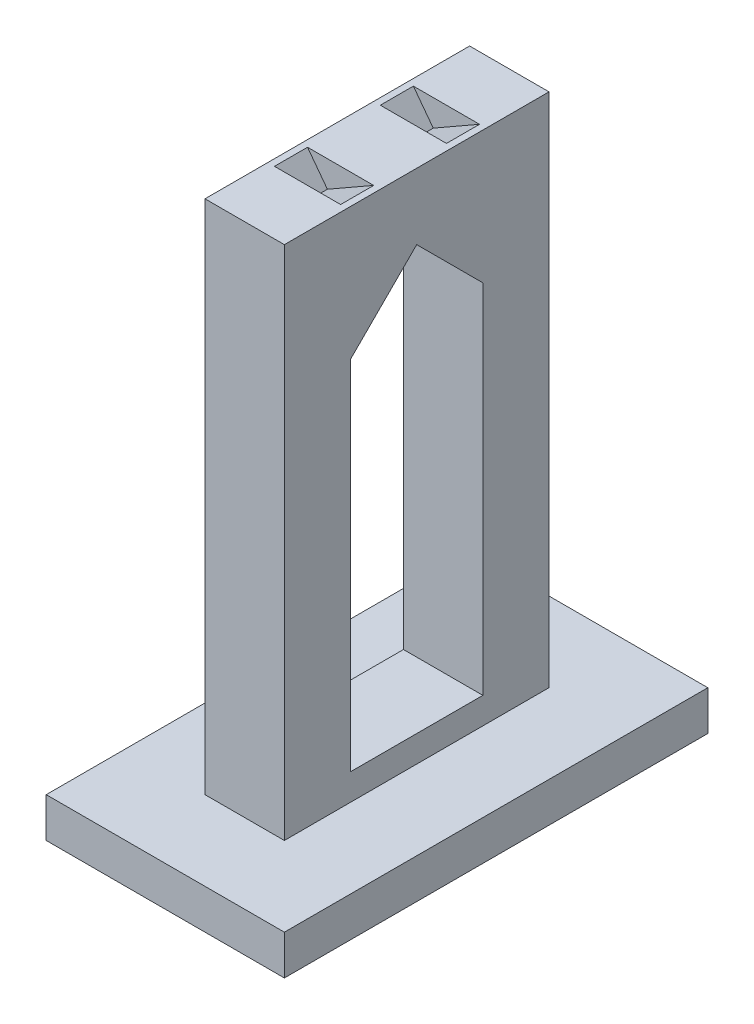
SolidWorks part; units mm, degrees
material "ABS"
ref_plane "Front Plane" through (0, 0, 0) normal (0, 0, 1) x (1, 0, 0)
ref_plane "Top Plane" through (0, 0, 0) normal (0, 1, 0) x (1, 0, 0)
ref_plane "Right Plane" through (0, 0, 0) normal (1, 0, 0) x (0, 0, -1)
sketch "Sketch2" plane through (0, 0, 0) normal (1, 0, 0) x (0, 0, -1)
  line L1 (-12.7, 53.34) -> (12.7, 53.34)
  line L2 (-12.7, 53.34) -> (-12.7, 0)
  line L3 (-12.7, 0) -> (12.7, 0)
  line L4 (12.7, 53.34) -> (12.7, 0)
  point P4 (0, 0)
  dimension "D1" = 25.4
  dimension "D2" = 2.54
extrude "Boss-Extrude1" add sketch "Sketch2" along normal mid plane 7.62
sketch "Sketch5" plane through (3.81, 0, 0) normal (1, 0, 0) x (0, 0, -1)
  line L8 (-6.35, 6.35) -> (6.35, 6.35)
  line L9 (6.35, 6.35) -> (6.35, 46.99)
  line L10 (6.35, 46.99) -> (-6.35, 46.99)
  line L11 (-6.35, 46.99) -> (-6.35, 6.35)
  line L13 (6.35, 6.35) -> (6.35, 46.99)
  line L14 (6.35, 46.99) -> (-6.35, 46.99)
  line L15 (-6.35, 46.99) -> (-6.35, 6.35)
  line L16 (-6.35, 6.35) -> (6.35, 6.35)
  dimension "D1" = 6.35
extrude "Cut-Extrude2" cut sketch "Sketch5" against normal through all
sketch "Sketch3" plane through (0, 0, 0) normal (0, 0, 1) x (1, 0, 0)
  line L0 (-3.175, 53.34) -> (-1.27, 50.8)
  line L1 (3.81, 53.34) -> (-3.81, 53.34) construction
  line L3 (-1.27, 50.8) -> (3.175, 53.34)
  line L4 (3.175, 53.34) -> (-3.175, 53.34)
  point P10 (0, 53.34)
  dimension "D1" = 2.54
  dimension "D2" = 6.35
  dimension "D3" = 1.905
extrude "Cut-Extrude1" cut sketch "Sketch3" against normal mid plane 13.335
extrude "Boss-Extrude2" add sketch "Sketch3<2>" along normal mid plane 6.985
sketch "Sketch3<2>" plane through (0, 0, 0) normal (0, 0, 1) x (1, 0, 0) same geometry as "Sketch3"
sketch "Sketch4" plane through (0, 0, 0) normal (0, 1, 0) x (1, 0, 0)
  line L8 (-11.43, 20.32) -> (-11.43, -20.32)
  line L9 (11.43, 20.32) -> (-11.43, 20.32)
  line L10 (11.43, -20.32) -> (11.43, 20.32)
  line L11 (-11.43, -20.32) -> (11.43, -20.32)
  line L12 (-11.43, 20.32) -> (-11.43, -20.32)
  line L13 (11.43, 20.32) -> (-11.43, 20.32)
  line L14 (11.43, -20.32) -> (11.43, 20.32)
  line L15 (-11.43, -20.32) -> (11.43, -20.32)
  dimension "D1" = 7.62
extrude "Boss-Extrude3" add sketch "Sketch4" along normal blind 3.81
chamfer "Chamfer1" distance 6.35 angle 45 2 edges at (0, 46.99, 6.35) (0, 46.99, -6.35)
